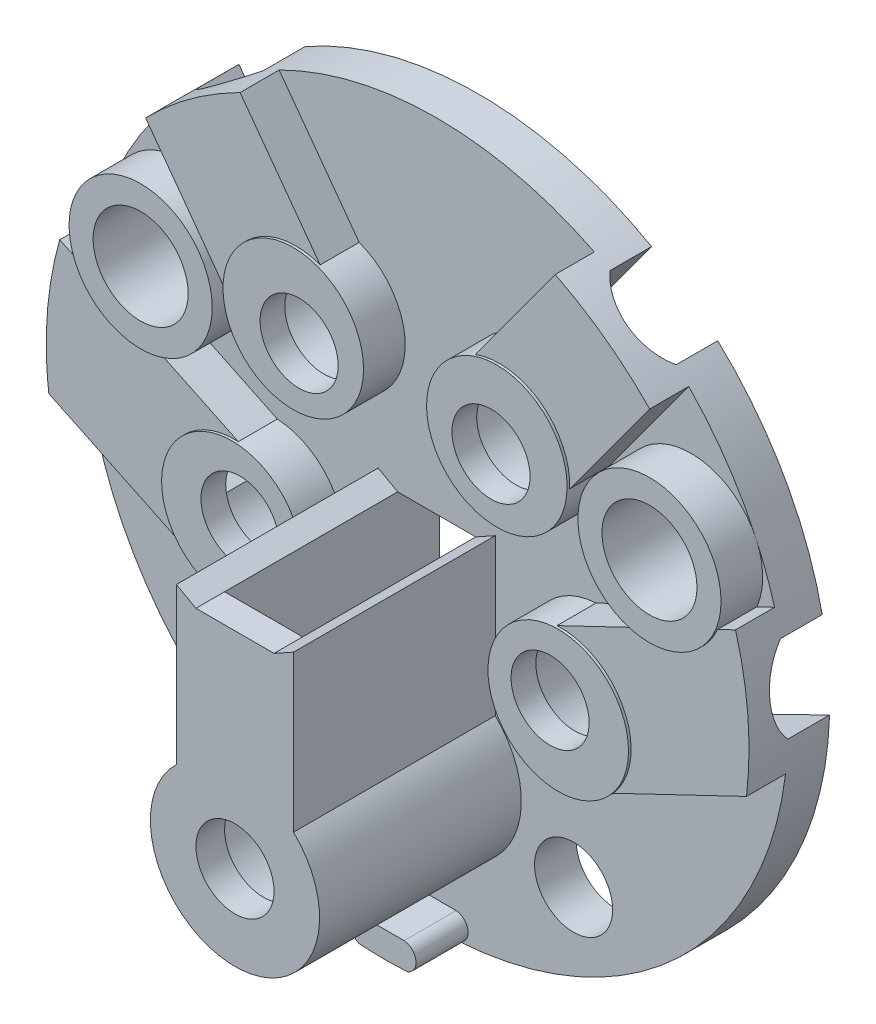
SolidWorks part; units mm, degrees
ref_plane "Front Plane" through (0, 0, 0) normal (0, 0, 1) x (1, 0, 0)
ref_plane "Top Plane" through (0, 0, 0) normal (0, 1, 0) x (1, 0, 0)
ref_plane "Right Plane" through (0, 0, 0) normal (1, 0, 0) x (0, 0, -1)
sketch "Sketch1" plane through (0, 0, 0) normal (0, 0, 1) x (1, 0, 0)
  circle A0 centre (0, 0) radius 27
  dimension "D1" = 54
extrude "Boss-Extrude1" add sketch "Sketch1" along normal blind 3.2
sketch "Sketch2" plane through (0, 0, 3.2) normal (0, 0, 1) x (1, 0, 0)
  line L0 (-236.4959, -273.0632) -> (-235.0824, -327.0447) construction
  line L2 (13.2147, 10.4187) -> (19.3668, 18.813)
  line L3 (5.9555, 15.7388) -> (12.1075, 24.1331)
  line L6 (16.5563, -8.163) -> (26.8035, -3.2515)
  line L7 (12.2426, 0.837) -> (18.1017, 3.6453)
  line L9 (0, 0) -> (0, -50000) construction
  line L11 (4.5, -10.5318) -> (4.5, 1.4492)
  line L12 (-4.5, -10.5318) -> (-4.5, 1.4492)
  line L14 (-3, 0.6159) -> (3, 0.6159)
  line L15 (-4.5, 1.4492) -> (-3, 0.6159)
  line L16 (3, 0.6159) -> (4.5, 1.4492)
  line L17 (24.5901, 6.7552) -> (25.9624, 7.413)
  line L18 (-1.591, -26) -> (1.409, -26)
  line L19 (-1.5, -25) -> (1.5, -25)
  line L20 (-16.5563, -8.163) -> (-26.8035, -3.2515)
  line L21 (-24.5901, 6.7552) -> (-25.9624, 7.413)
  line L22 (-12.2426, 0.837) -> (-18.1017, 3.6453)
  line L23 (-13.2147, 10.4187) -> (-19.3668, 18.813)
  line L24 (-5.9555, 15.7388) -> (-12.1075, 24.1331)
  circle A0 centre (7.3725, 9.9172) radius 3
  arc A1 (13.2147, 10.4187) -> (5.9555, 15.7388) centre (7.8206, 10.6711) ccw
  arc A3 (18.1017, 3.6453) -> (24.5901, 6.7552) centre (19.5478, 8.9518) ccw
  circle A4 centre (19.5478, 8.9518) radius 3.65
  circle A5 centre (11.9124, -4.1945) radius 3
  arc A6 (16.5563, -8.163) -> (12.2426, 0.837) centre (12.5387, -4.5549) ccw
  circle A7 centre (10.5169, -18.9353) radius 3
  circle A8 centre (0, -15.2222) radius 3
  arc A9 (-4.5, -10.5318) -> (4.5, -10.5318) centre (0, -15.2222) ccw
  arc A10 (-1.9754, -26.9276) -> (1.7541, -26.943) centre (0, 0) ccw
  arc A11 (-1.5, -25) -> (-1.9754, -26.9276) centre (-1.591, -26) ccw
  arc A12 (1.7541, -26.943) -> (1.5, -25) centre (1.409, -26) ccw
  arc A13 (19.3668, 18.813) -> (12.1075, 24.1331) centre (0, 0) ccw
  arc A14 (26.8035, -3.2515) -> (25.9624, 7.413) centre (0, 0) ccw
  circle A15 centre (7.8206, 10.6711) radius 5.4
  circle A16 centre (19.5478, 8.9518) radius 5.5
  circle A17 centre (12.5387, -4.5549) radius 5.4
  circle A18 centre (-11.9124, -4.1945) radius 3
  circle A19 centre (-12.5387, -4.5549) radius 5.4
  arc A20 (-26.8035, -3.2515) -> (-25.9624, 7.413) centre (0, 0) cw
  arc A21 (-18.1017, 3.6453) -> (-24.5901, 6.7552) centre (-19.5478, 8.9518) cw
  arc A22 (-16.5563, -8.163) -> (-12.2426, 0.837) centre (-12.5387, -4.5549) cw
  circle A23 centre (-19.5478, 8.9518) radius 3.65
  circle A24 centre (-19.5478, 8.9518) radius 5.5
  circle A25 centre (-7.3725, 9.9172) radius 3
  circle A26 centre (-7.8206, 10.6711) radius 5.4
  arc A27 (-19.3668, 18.813) -> (-12.1075, 24.1331) centre (0, 0) cw
  arc A28 (-13.2147, 10.4187) -> (-5.9555, 15.7388) centre (-7.8206, 10.6711) cw
  point P39 (0, 0.6159)
  point P43 (0, -26)
  dimension "D2" = 6
  dimension "D3" = 11
  dimension "D5" = 10.8
  dimension "D6" = 7.3
  dimension "D7" = 6
  dimension "D10" = 6
  dimension "D11" = 6
  dimension "D12" = 13
  dimension "D15" = 54
  dimension "D9" = 10.8
  dimension "D1" = 54
  dimension "D4" = 9
  dimension "D13" = 9
  dimension "D14" = 6
  dimension "D16" = 3
sketch "Sketch3" plane through (0, 0, 0) normal (0, 0, 1) x (1, 0, 0)
  line L0 (-236.4959, -273.0632) -> (-235.0824, -327.0447) construction
  line L2 (13.2147, 10.4187) -> (19.3668, 18.813)
  line L3 (5.9555, 15.7388) -> (12.1075, 24.1331)
  line L6 (16.5563, -8.163) -> (26.8035, -3.2515)
  line L7 (12.2426, 0.837) -> (18.1017, 3.6453)
  line L9 (0, 0) -> (0, -50000) construction
  line L11 (4.5, -10.5318) -> (4.5, 1.4492)
  line L12 (-4.5, -10.5318) -> (-4.5, 1.4492)
  line L14 (-3, 0.6159) -> (3, 0.6159)
  line L15 (-4.5, 1.4492) -> (-3, 0.6159)
  line L16 (3, 0.6159) -> (4.5, 1.4492)
  line L17 (24.5901, 6.7552) -> (25.9624, 7.413)
  line L18 (-1.591, -26) -> (1.409, -26)
  line L19 (-1.5, -25) -> (1.5, -25)
  line L20 (-16.5563, -8.163) -> (-26.8035, -3.2515)
  line L21 (-24.5901, 6.7552) -> (-25.9624, 7.413)
  line L22 (-12.2426, 0.837) -> (-18.1017, 3.6453)
  line L23 (-13.2147, 10.4187) -> (-19.3668, 18.813)
  line L24 (-5.9555, 15.7388) -> (-12.1075, 24.1331)
  circle A0 centre (7.3725, 9.9172) radius 3
  arc A1 (13.2147, 10.4187) -> (5.9555, 15.7388) centre (7.8206, 10.6711) ccw
  arc A3 (18.1017, 3.6453) -> (24.5901, 6.7552) centre (19.5478, 8.9518) ccw
  circle A4 centre (19.5478, 8.9518) radius 3.65
  circle A5 centre (11.9124, -4.1945) radius 3
  arc A6 (16.5563, -8.163) -> (12.2426, 0.837) centre (12.5387, -4.5549) ccw
  circle A7 centre (10.5169, -18.9353) radius 3
  circle A8 centre (0, -15.2222) radius 3
  arc A9 (-4.5, -10.5318) -> (4.5, -10.5318) centre (0, -15.2222) ccw
  arc A10 (-1.9754, -26.9276) -> (1.7541, -26.943) centre (0, 0) ccw
  arc A11 (-1.5, -25) -> (-1.9754, -26.9276) centre (-1.591, -26) ccw
  arc A12 (1.7541, -26.943) -> (1.5, -25) centre (1.409, -26) ccw
  arc A13 (19.3668, 18.813) -> (12.1075, 24.1331) centre (0, 0) ccw
  arc A14 (26.8035, -3.2515) -> (25.9624, 7.413) centre (0, 0) ccw
  circle A15 centre (7.8206, 10.6711) radius 5.4
  circle A16 centre (19.5478, 8.9518) radius 5.5
  circle A17 centre (12.5387, -4.5549) radius 5.4
  circle A18 centre (-11.9124, -4.1945) radius 3
  circle A19 centre (-12.5387, -4.5549) radius 5.4
  arc A20 (-26.8035, -3.2515) -> (-25.9624, 7.413) centre (0, 0) cw
  arc A21 (-18.1017, 3.6453) -> (-24.5901, 6.7552) centre (-19.5478, 8.9518) cw
  arc A22 (-16.5563, -8.163) -> (-12.2426, 0.837) centre (-12.5387, -4.5549) cw
  circle A23 centre (-19.5478, 8.9518) radius 3.65
  circle A24 centre (-19.5478, 8.9518) radius 5.5
  circle A25 centre (-7.3725, 9.9172) radius 3
  circle A26 centre (-7.8206, 10.6711) radius 5.4
  arc A27 (-19.3668, 18.813) -> (-12.1075, 24.1331) centre (0, 0) cw
  arc A28 (-13.2147, 10.4187) -> (-5.9555, 15.7388) centre (-7.8206, 10.6711) cw
  point P39 (0, 0.6159)
  point P43 (0, -26)
  dimension "D2" = 6
  dimension "D3" = 11
  dimension "D5" = 10.8
  dimension "D6" = 7.3
  dimension "D7" = 6
  dimension "D10" = 6
  dimension "D11" = 6
  dimension "D12" = 13
  dimension "D15" = 54
  dimension "D9" = 10.8
  dimension "D1" = 54
  dimension "D4" = 9
  dimension "D13" = 9
  dimension "D14" = 6
  dimension "D16" = 3
extrude "Boss-Extrude2" add sketch "Sketch2" along normal blind 3 contours L2 A13 L3 A1 | A27 L23 A26 L24 | L22 A21 L21 A20 L20 A19 | L6 A14 L17 A3 L7 A6 region at (13.2229, 18.0424, 3.2) region at (21.5442, -0.2143, 3.2) region at (-21.5442, -0.2143, 3.2) region at (-13.2229, 18.0424, 3.2)
extrude "Boss-Extrude3" add sketch "Sketch2<4>" along normal blind 3.2 contours A19 A18 | A24 A21 A23 | A26 A25 | A1 A15 A0 | A16 A3 A4 | A6 A17 A5 region at (4.7188, 6.4388, 3.2) region at (7.8069, -6.8228, 3.2) region at (16.3033, 13.1987, 3.2) region at (-17.2705, -2.2869, 3.2) region at (-21.8577, 4.1324, 3.2) region at (-10.9224, 14.9035, 3.2)
sketch "Sketch2<4>" plane through (0, 0, 3.2) normal (0, 0, 1) x (1, 0, 0) same geometry as "Sketch2"
extrude "Boss-Extrude4" add sketch "Sketch2<5>" along normal blind 15.5 contours L12 A9 L11 L16 L14 L15 A8 region at (0, -10.1451, 3.2)
sketch "Sketch2<5>" plane through (0, 0, 3.2) normal (0, 0, 1) x (1, 0, 0) same geometry as "Sketch2"
extrude "Boss-Extrude5" add sketch "Sketch2<6>" along normal blind 4 contours A12 L19 A11 region at (-0.0895, -25.9927, 3.2)
sketch "Sketch2<6>" plane through (0, 0, 3.2) normal (0, 0, 1) x (1, 0, 0) same geometry as "Sketch2"
extrude "Cut-Extrude1" cut sketch "Sketch2<7>" against normal through all contours A23 | A18 | A25 | A0 | A4 | A5 | A7 | A8 region at (7.3725, 9.9172, 3.2) region at (19.5478, 8.9518, 3.2) region at (11.9124, -4.1945, 3.2) region at (10.5169, -18.9353, 3.2) region at (0, -15.2222, 3.2) region at (-11.9124, -4.1945, 3.2) region at (-19.5478, 8.9518, 3.2) region at (-7.3725, 9.9172, 3.2)
sketch "Sketch2<7>" plane through (0, 0, 3.2) normal (0, 0, 1) x (1, 0, 0) same geometry as "Sketch2"
sketch "Sketch4" plane through (0, 0, 0) normal (0, 0, -1) x (-1, 0, 0)
  line L4 (-588.0348, -802.3627) -> (5.4561, 7.4448) construction
  line L5 (5.9555, 15.7388) -> (12.1075, 24.1331) construction
  line L10 (6.7372, 14.5216) -> (15.0504, 25.8648)
  line L12 (15.0504, 25.8648) -> (20.1319, 22.1407)
  line L13 (11.8186, 10.7975) -> (20.1319, 22.1407)
  line L14 (10.1851, 13.8974) -> (607.0868, 828.3588) construction
  line L15 (13.6008, -0.6984) -> (28.3883, 6.5177)
  line L16 (28.3883, 6.5177) -> (31.0196, 1.1255)
  line L17 (16.2321, -6.0907) -> (31.0196, 1.1255)
  line L19 (12.5444, -4.5521) -> (26.7913, 2.4002) construction
  arc A0 (11.8186, 10.7975) -> (6.7372, 14.5216) centre (7.8206, 10.6711) ccw
  arc A1 (16.2321, -6.0907) -> (13.6008, -0.6984) centre (12.5387, -4.5549) ccw
  point P9 (17.5911, 24.0028)
  point P19 (29.704, 3.8216)
  point P22 (0, 0)
  point P23 (0, 0)
  dimension "D1" = 8
  dimension "D2" = 6.3
  dimension "D3" = 6
extrude "Cut-Extrude2" cut sketch "Sketch4" against normal blind 3.2 contours L10 L12 L13 A0 | L15 L16 L17 A1
sketch "Sketch6" plane through (0, 0, 0) normal (0, 0, -1) x (-1, 0, 0)
  circle A0 centre (7.8206, 10.6711) radius 4
  circle A1 centre (12.5387, -4.5549) radius 4
  circle M6 centre (11.9124, -4.1945) radius 3
  arc M14 (16.2321, -6.0907) -> (13.6008, -0.6984) centre (12.5387, -4.5549) ccw
extrude "Cut-Extrude3" cut sketch "Sketch6" against normal blind 4.5 contours A1 M14 M6 | A0 region at (-16.3504, -5.3158, 0)
ref_plane "Plane3" through (-15.8514, 21.6289, 0) normal (-0.5911, 0.8066, 0) x (0.8066, 0.5911, 0)
sketch "Sketch11" plane through (-15.8514, 21.6289, 0) normal (-0.5911, 0.8066, 0) x (0.8066, 0.5911, 0)
  line L1 (0, -3.2) -> (0, -50003.2) construction
  line L2 (3.15, -3.2) -> (-3.15, -3.2) construction
  line L3 (-3.15, -3.2) -> (3.15, -3.2)
  arc A1 (-3.15, -3.2) -> (3.15, -3.2) centre (0, -0.0337) ccw
  point P5 (0, -3.2)
  point P6 (0, -4.5)
  dimension "D1" = 1.3
ref_plane "Plane4" through (-23.5306, 11.4826, 0) normal (-0.8987, 0.4386, 0) x (0, 0, 1)
sketch "Sketch12" plane through (-23.5306, 11.4826, 26.1828) normal (-0.8987, 0.4386, 0) x (0.1923, 0.3941, 0.8987)
  line L1 (0, -3.2) -> (0, -50003.2) construction
  line L3 (-26.1772, -1.2376) -> (-23.5459, 4.1547)
  line L5 (-23.6454, 3.9506) -> (-21951.4451, -44931.2427) construction
  line L6 (-23.5459, 4.1547) -> (-26.4217, 5.558) construction
  arc A1 (-26.1772, -1.2376) -> (-23.5459, 4.1547) centre (-27.3883, 2.6916) ccw
  point P6 (-27.3883, -1.42)
  point P8 (-25.8083, -0.4815)
  point P9 (-23.6932, 0.8884)
  point P10 (-24.8616, 1.4585)
  point P18 (-26.0777, -1.0336)
  dimension "D1" = 1.3
extrude "Cut-Extrude4" cut sketch "Sketch12" against normal up to next and the other way through all
extrude "Cut-Extrude5" cut sketch "Sketch11" against normal up to next and the other way through all
mirror "Mirror3" about plane through (0, 0, 0) normal (1, 0, 0) of "Cut-Extrude3", "Cut-Extrude4", "Cut-Extrude2"
mirror "Mirror4" about plane through (0, 0, 0) normal (1, 0, 0) of "Cut-Extrude5"
sketch "Sketch13" plane through (0, 0, 0) normal (0, 0, -1) x (-1, 0, 0)
  line L0 (-3, 0.6159) -> (3, 0.6159)
  line L1 (-3, 0.6159) -> (-3, -11.5395)
  line L2 (3, 0.6159) -> (3, -11.5395)
  arc A0 (-3, -11.5395) -> (3, -11.5395) centre (0, -15.2222) ccw
  point P3 (0, 0)
  dimension "D1" = 9.5
extrude "Cut-Extrude6" cut sketch "Sketch13" against normal blind 16.5
